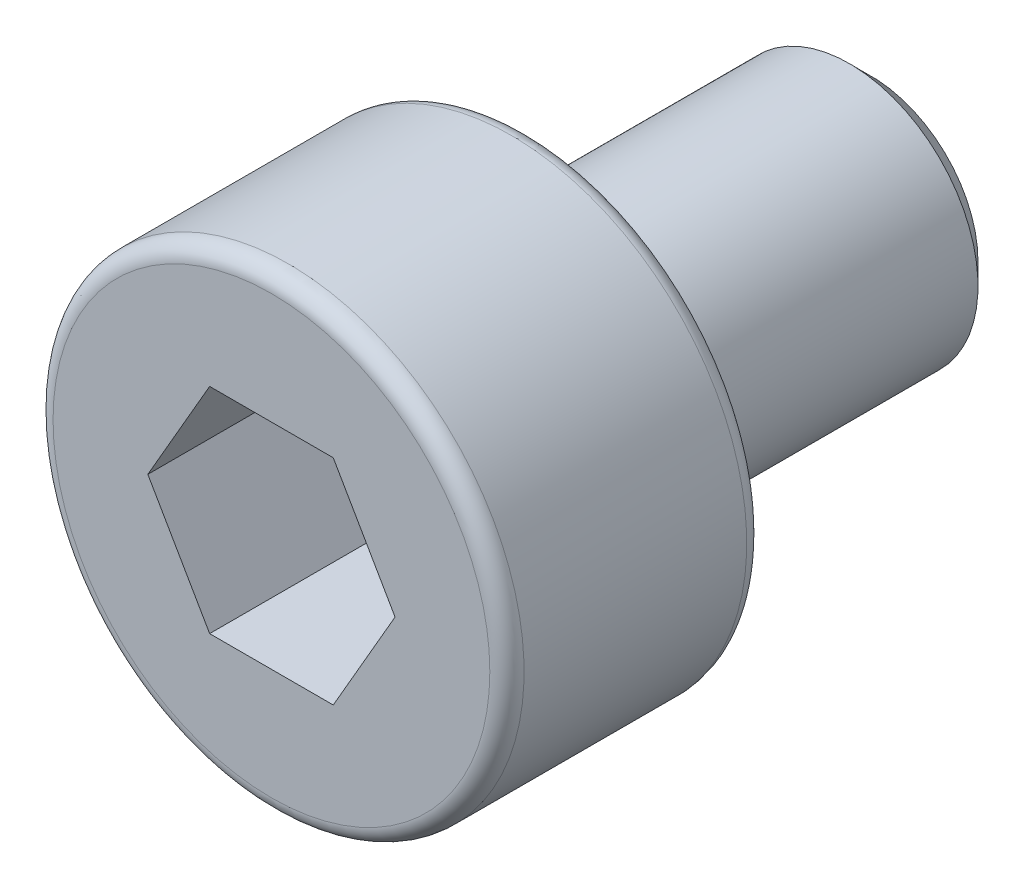
SolidWorks part; units mm, degrees
ref_plane "Front Plane" through (0, 0, 0) normal (0, 0, 1) x (1, 0, 0)
ref_plane "Top Plane" through (0, 0, 0) normal (0, 1, 0) x (1, 0, 0)
ref_plane "Right Plane" through (0, 0, 0) normal (1, 0, 0) x (0, 0, -1)
ref_plane "Plane1" through (0, 0, 7) normal (0, 0, 1) x (1, 0, 0)
sketch "Sketch1" plane through (0, 0, 7) normal (0, 0, 1) x (1, 0, 0)
  circle A0 centre (0, 0) radius 2.75
extrude "Boss-Extrude1" add sketch "Sketch1" against normal blind 3
sketch "Sketch2" plane through (0, 0, 4) normal (0, 0, -1) x (-1, 0, 0)
  circle A0 centre (0, 0) radius 1.5
extrude "Boss-Extrude2" add sketch "Sketch2" along normal blind 4
sketch "Sketch3" plane through (0, 0, 7) normal (0, 0, 1) x (1, 0, 0)
  line L0 (-1.4434, 0) -> (-0.7217, -1.25)
  line L1 (-0.7217, -1.25) -> (0.7217, -1.25)
  line L2 (0.7217, -1.25) -> (1.4434, 0)
  line L3 (1.4434, 0) -> (0.7217, 1.25)
  line L4 (0.7217, 1.25) -> (-0.7217, 1.25)
  line L5 (-0.7217, 1.25) -> (-1.4434, 0)
extrude "Cut-Extrude1" cut sketch "Sketch3" against normal blind 2
chamfer "Chamfer1" distance 0.25 angle 45 1 edges at (-1.5, 0, 0)
fillet "Fillet1" radius 0.2 2 edges at (-2.75, 0, 4) (-2.75, 0, 7) tangent propagation no
ref_axis "Axis1" through (0, 0, -1.2702) along (0, 0, 1)
